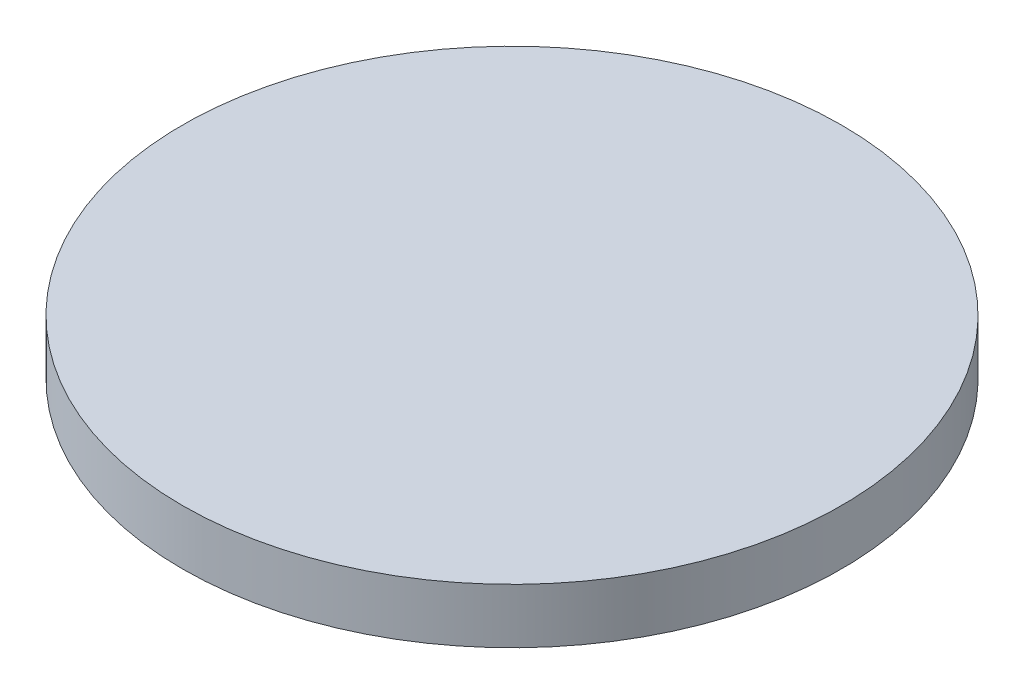
SolidWorks part; units mm, degrees
ref_plane "Front Plane" through (0, 0, 0) normal (0, 0, 1) x (1, 0, 0)
ref_plane "Top Plane" through (0, 0, 0) normal (0, 1, 0) x (1, 0, 0)
ref_plane "Right Plane" through (0, 0, 0) normal (1, 0, 0) x (0, 0, -1)
sketch "Sketch1" plane through (0, 0, 0) normal (0, 1, 0) x (1, 0, 0)
  circle A0 centre (-40.7144, 6.5655) radius 38.1
extrude "Boss-Extrude1" add sketch "Sketch1" along normal blind 6.35
